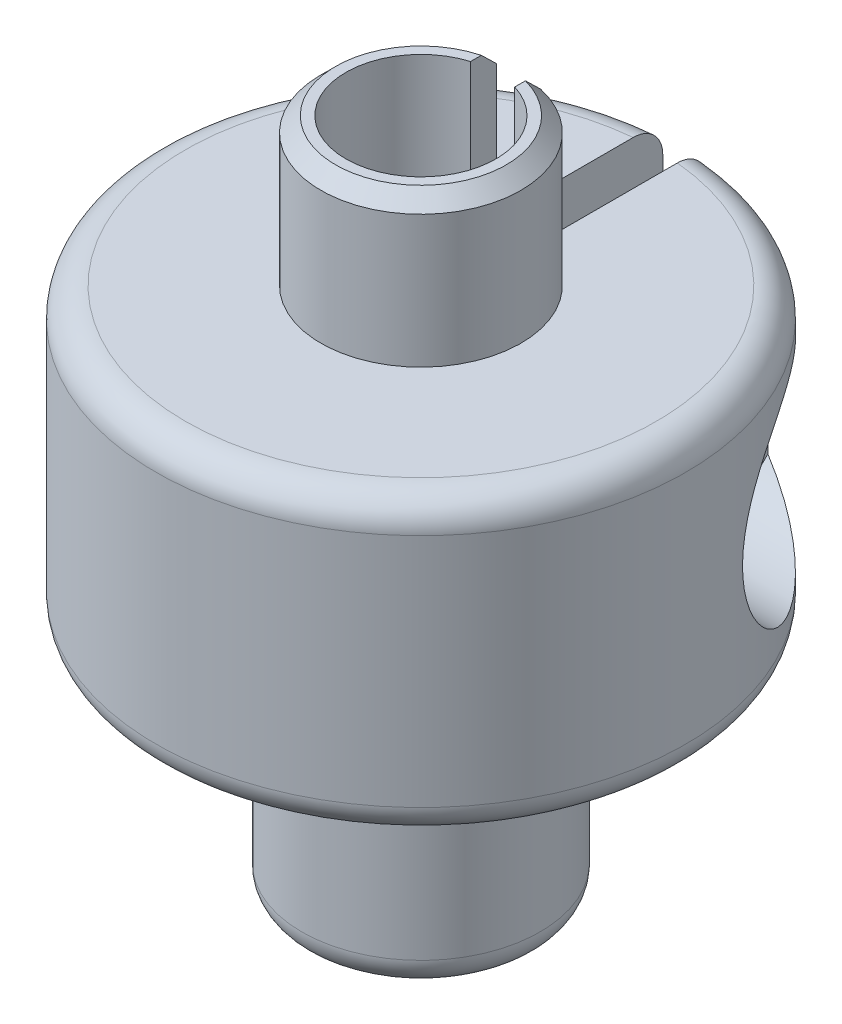
SolidWorks part; units mm, degrees
ref_plane "Front Plane" through (0, 0, 0) normal (0, 0, 1) x (1, 0, 0)
ref_plane "Top Plane" through (0, 0, 0) normal (0, 1, 0) x (1, 0, 0)
ref_plane "Right Plane" through (0, 0, 0) normal (1, 0, 0) x (0, 0, -1)
sketch "Sketch1" plane through (0, 0, 0) normal (0, 1, 0) x (1, 0, 0)
  circle A0 centre (0, 0) radius 4.05
  dimension "D1" = 8.1
extrude "Boss-Extrude1" add sketch "Sketch1" along normal blind 8
sketch "Sketch2" plane through (0, 8, 0) normal (0, 1, 0) x (1, 0, 0)
  circle A0 centre (0, 0) radius 9
  dimension "D1" = 18
extrude "Boss-Extrude2" add sketch "Sketch2" along normal blind 10
fillet "Fillet1" radius 1 3 edges at (0, 0, 4.05) (0, 8, 9) (0, 18, 9)
sketch "Sketch3" plane through (0, 18, 0) normal (0, 1, 0) x (1, 0, 0)
  circle A0 centre (0, 0) radius 2.55
  dimension "D1" = 5.1
extrude "Cut-Extrude1" cut sketch "Sketch3" against normal blind 10 contours A0
sketch "Sketch20" plane through (0, 18, 0) normal (0, 1, 0) x (1, 0, 0)
  line L1 (-0.75, 2.4372) -> (0.75, 2.4372)
  line L2 (-0.75, 2.4372) -> (-0.75, 8.9687)
  line L4 (0.75, 2.4372) -> (0.75, 8.9687)
  circle A0 centre (0, 0) radius 2.55 construction
  circle A1 centre (0, 0) radius 2.55 construction
  circle A2 centre (0, 0) radius 9 construction
  arc A3 (0.75, 8.9687) -> (-0.75, 8.9687) centre (0, 0) ccw
  dimension "D1" = 1.5
extrude "Cut-Extrude2" cut sketch "Sketch20" against normal up to surface (10 mm away) up to face at (0, 8, 8)
ref_plane "Plane2" through (10, 0, 0) normal (1, 0, 0) x (0, 0, -1)
hole_wizard "M3 Clearance Hole1" positions "Sketch32" profile "Sketch26" hole size "M3" standard "ANSI Metric" end condition through all
sketch "Sketch32" plane through (10, 0, 0) normal (1, 0, 0) x (0, 0, -1)
  line L0 (8.9687, 9) -> (8.9687, 17) construction
  line L1 (8.9687, 9) -> (8.9687, 17) construction
  line L2 (2.4372, 8) -> (2.4372, 18) construction
  line L3 (2.4372, 8) -> (2.4372, 18) construction
  line L4 (2.4372, 13) -> (8.9687, 13) construction
  point P0 (5.703, 13)
  point P5 (8.9687, 13)
  point P17 (5.703, 13)
sketch "Sketch26" plane through (10, 13, -5.703) normal (0, 1, 0) x (0, 0, -1)
  line L0 (0, 0) -> (0, 19)
  line L1 (0, 19) -> (1.7, 19)
  line L2 (1.7, 19) -> (1.7, 0)
  line L5 (1.7, 0) -> (0, 0)
  line L11 (0, -6.35) -> (0, 107.95) construction
  dimension "Thru Hole Dia." = 3.4
  dimension "Thru Hole Depth" = 19
sketch "Sketch28" plane through (10, 0, 0) normal (1, 0, 0) x (0, 0, -1)
  circle A0 centre (5.703, 13) radius 1.7 construction
  circle A1 centre (5.703, 13) radius 1.7 construction
  circle A2 centre (5.703, 13) radius 3.5
  dimension "D1" = 7
extrude "Cut-Extrude3" cut sketch "Sketch28" against normal blind 6.5
mirror "Mirror1" about plane through (0, 0, 0) normal (1, 0, 0) of "Cut-Extrude3"
sketch "Sketch29" plane through (0, 0, 0) normal (0, 0, 1) x (1, 0, 0)
  line L0 (-4.05, 8) -> (-4.05, 1) construction
  line L1 (4.05, 8) -> (-4.05, 8)
  line L2 (4.05, 8) -> (4.05, 7.5)
  line L3 (4.05, 7.5) -> (-4.05, 7.5)
  line L4 (-4.05, 8) -> (-4.05, 7.5)
  dimension "D1" = 0.5
extrude "Cut-Extrude7" cut sketch "Sketch29" against normal through all
fillet "Fillet2" radius 0.25 3 edges at (3.3, 8, 0) (-3.3, 8, 0) (0, 7.5, 0)
sketch "Sketch30" plane through (0, 18, 0) normal (0, 1, 0) x (1, 0, 0)
  line L0 (-0.75, 7.9648) -> (-0.75, 2.4372) construction
  line L1 (0.75, 2.4372) -> (0.75, 7.9648) construction
  line L2 (-0.75, 3.3162) -> (-0.75, 2.4372)
  line L3 (0.75, 2.4372) -> (0.75, 3.3162)
  arc A0 (-0.75, 2.4372) -> (0.75, 2.4372) centre (0, 0) ccw
  arc A1 (-0.75, 3.3162) -> (0.75, 3.3162) centre (0, 0) ccw
  dimension "D1" = 3.4
extrude "Boss-Extrude3" add sketch "Sketch30" along normal blind 5
chamfer "Chamfer1" distance 0.5 angle 45 1 edges at (0, 23, 3.4)
equation "\"1.5.00mm\"=6"
